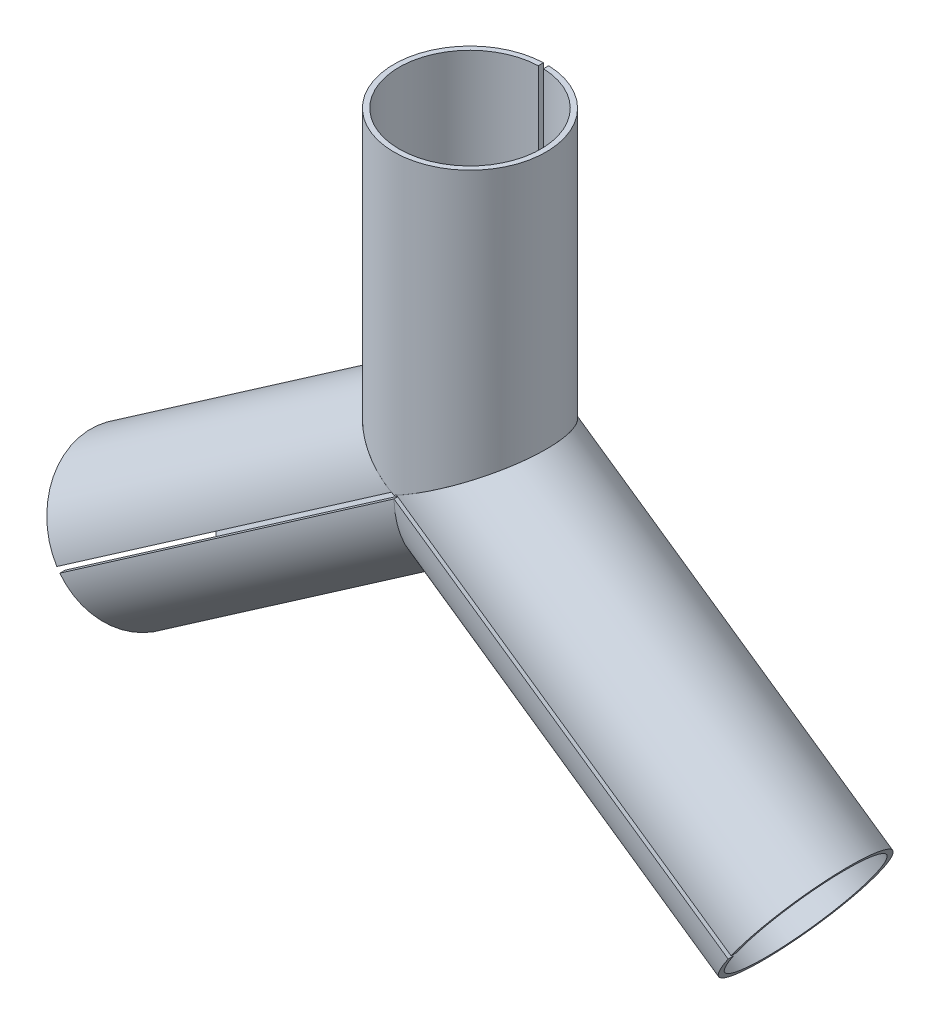
SolidWorks part; units mm, degrees
ref_plane "前视基准面" through (0, 0, 0) normal (0, 0, 1) x (1, 0, 0)
ref_plane "上视基准面" through (0, 0, 0) normal (0, 1, 0) x (1, 0, 0)
ref_plane "右视基准面" through (0, 0, 0) normal (1, 0, 0) x (0, 0, -1)
sketch "草图1" plane through (0, 0, 0) normal (0, 0, 1) x (1, 0, 0)
  line L0 (-64.7494, -44.8345) -> (0, 0) construction
  line L1 (0, 0) -> (64.7494, -44.8345) construction
  line L2 (0, 0) -> (0, 57.3433) construction
  line L3 (-14.6769, 57.3433) -> (14.6769, 57.3433) construction
  line L4 (0, 0) -> (0, -44.8345) construction
  line L5 (0, -44.8345) -> (0, -45.8345) construction
  line L6 (0, 0) -> (0, 57.3433)
  line L7 (56.3942, -56.901) -> (73.1046, -32.768) construction
  line L8 (14.6769, 57.3433) -> (14.6769, 7.6892) construction
  line L9 (14.6769, 7.6892) -> (73.1046, -32.768) construction
  line L10 (-14.6769, 57.3433) -> (-14.6769, 7.6892) construction
  line L11 (-14.6769, 7.6892) -> (0, 0) construction
  line L12 (0, 0) -> (14.6769, 7.6892) construction
  line L13 (56.3942, -56.901) -> (0, -17.8519) construction
  dimension "R" = 14.6769
  dimension "L1" = 57.3433
  dimension "L2" = 78.7567
  dimension "B" = 110.6
  dimension "t" = 1
sketch "草图2" plane through (0, 0, 0) normal (0, 1, 0) x (1, 0, 0)
  circle A0 centre (0, 0) radius 14.6769
extrude "拉伸-薄壁1" add sketch "草图2" along normal up to vertex (57.3433 mm away) thin up to point (0, 57.3433, 0) thin type one direction reverse wall 1
ref_plane "基准面1" through (64.7494, -44.8345, 0) normal (0.8221, -0.5693, 0) x (0, 0, -1)
sketch "草图3" plane through (64.7494, -44.8345, 0) normal (0.8221, -0.5693, 0) x (0, 0, -1)
  circle A0 centre (0, 0) radius 14.6769
extrude "拉伸-薄壁2" add sketch "草图3" against normal up to vertex (78.7567 mm away) separate body thin up to point (0, 0, 0) thin type one direction reverse wall 1
sketch "草图4" plane through (0, 0, 0) normal (0, 0, 1) x (1, 0, 0)
  line L0 (-29.3538, 15.3784) -> (0, 0)
  line L1 (0, 0) -> (29.3538, 15.3784)
  line L2 (-29.3538, 15.3784) -> (-29.3538, -44.8345)
  line L3 (-29.3538, -44.8345) -> (29.3538, -44.8345)
  line L4 (29.3538, -44.8345) -> (29.3538, 15.3784)
extrude "切除-拉伸1" cut sketch "草图4" against normal through all and the other way through all
sketch "草图5" plane through (0, 0, 0) normal (0, 0, 1) x (1, 0, 0)
  line L0 (29.3538, 15.3784) -> (0, 0)
  line L1 (0, 0) -> (0, -44.8345)
  line L2 (0, -44.8345) -> (-14.6769, -44.8345)
  line L3 (-14.6769, -44.8345) -> (-14.6769, 15.3784)
  line L4 (-14.6769, 15.3784) -> (29.3538, 15.3784)
extrude "切除-拉伸2" cut sketch "草图5" against normal through all and the other way through all
sketch "草图6" plane through (64.7494, -44.8345, 0) normal (0.8221, -0.5693, 0) x (0, 0, -1)
  line L0 (0, 0) -> (-14.6769, 0)
  line L1 (0, -14.6769) -> (0, 14.6769) construction
  circle A0 centre (0, 0) radius 14.6769 construction
extrude "切除-拉伸-薄壁1" cut sketch "草图6" against normal through all thin thin type mid plane wall 1
extrude "切除-拉伸-薄壁2" cut sketch "草图1" against normal through all thin thin type mid plane wall 1
mirror "镜向1" about plane through (0, 0, 0) normal (1, 0, 0) of bodies 105
equation "\"D5@拉伸-薄壁1\" = \"t@草图1\""
equation "\"D5@拉伸-薄壁2\" = \"t@草图1\""
